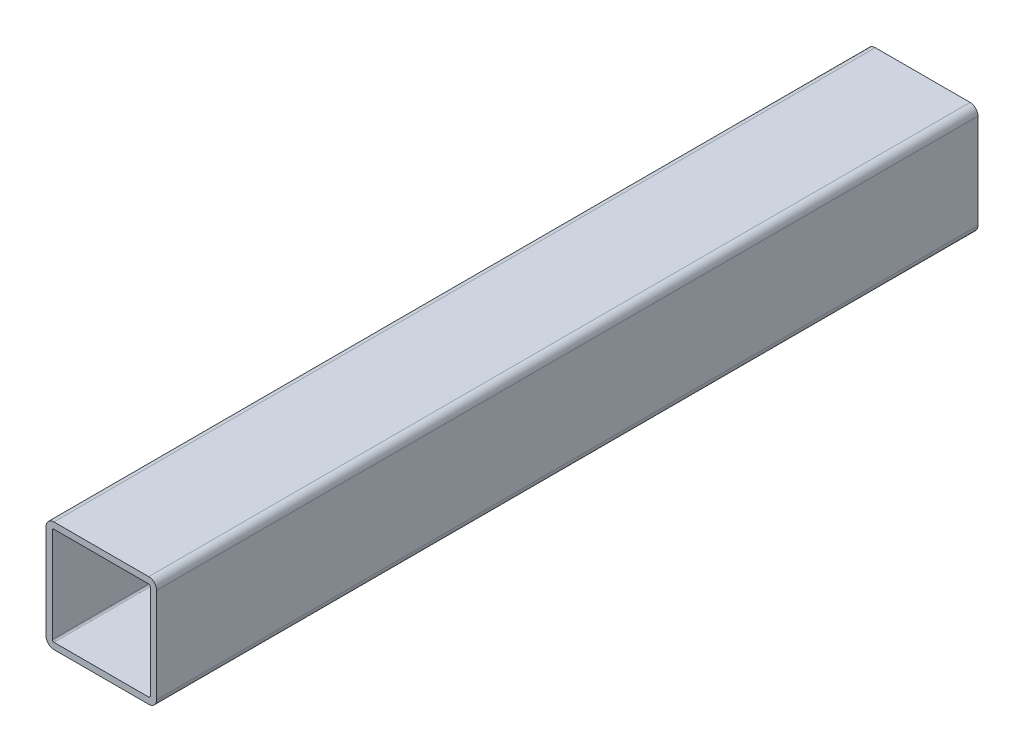
SolidWorks part; units mm, degrees
material "Plain Carbon Steel"
ref_plane "Front Plane" through (0, 0, 0) normal (0, 0, 1) x (1, 0, 0)
ref_plane "Top Plane" through (0, 0, 0) normal (0, 1, 0) x (1, 0, 0)
ref_plane "Right Plane" through (0, 0, 0) normal (1, 0, 0) x (0, 0, -1)
sketch "Sketch1" plane through (0, 0, 0) normal (0, 0, 1) x (1, 0, 0)
  line L0 (4, 5) -> (4, 65)
  line L1 (5, 0) -> (65, 0)
  line L2 (0, 5) -> (0, 65)
  line L3 (5, 70) -> (65, 70)
  line L4 (70, 5) -> (70, 65)
  line L5 (5, 66) -> (65, 66)
  line L6 (66, 5) -> (66, 65)
  line L7 (5, 4) -> (65, 4)
  arc A0 (5, 0) -> (0, 5) centre (5, 5) cw
  arc A1 (65, 0) -> (70, 5) centre (65, 5) ccw
  arc A2 (65, 70) -> (70, 65) centre (65, 65) cw
  arc A3 (0, 65) -> (5, 70) centre (5, 65) cw
  arc A4 (4, 65) -> (5, 66) centre (5, 65) cw
  arc A5 (65, 66) -> (66, 65) centre (65, 65) cw
  arc A6 (65, 4) -> (66, 5) centre (65, 5) ccw
  arc A7 (5, 4) -> (4, 5) centre (5, 5) cw
  point P7 (0, 0)
  point P12 (70, 70)
  point P15 (0, 70)
  dimension "D3" = 5
  dimension "D1" = 70
  dimension "D2" = 70
  dimension "D4" = 4
extrude "Boss-Extrude1" add sketch "Sketch1" along normal blind 520
sketch "Center_lines" plane through (0, 70, 0) normal (0, 1, 0) x (1, 0, 0)
  line L0 (35, 58.7626) -> (35, -578.7626) construction
  line L1 (0, -260) -> (70, -260) construction
  line L2 (65, 0) -> (5, 0) construction
  line L3 (65, -520) -> (65, 0) construction
  line L4 (0, -520) -> (0, 0) construction
  point P6 (35, 0)
  point P7 (35, -260)
  point P10 (65, -260)
  point P15 (35, -260)
sketch "Tube_end_reference" plane through (0, 0, 520) normal (0, 0, 1) x (1, 0, 0)
  line L0 (70, 5) -> (70, 65) construction
  line L1 (70, 70) -> (0, 70) construction
  line L2 (70, 70) -> (70, 0) construction
  line L3 (70, 0) -> (0, 0) construction
  line L4 (0, 70) -> (0, 0) construction
  line L5 (0, 65) -> (0, 5) construction
  line L6 (0, 70) -> (70, 70) construction
  line L7 (5, 0) -> (65, 0) construction
sketch "Tube_corners_R" plane through (70, 0, 0) normal (1, 0, 0) x (0, 0, -1)
  line L0 (-520, 0) -> (0, 0) construction
  line L1 (-520, 70) -> (0, 70) construction
sketch "Tube_corners_L" plane through (0, 0, 0) normal (-1, 0, 0) x (0, 0, 1)
  line L0 (520, 70) -> (0, 70) construction
  line L1 (520, 0) -> (0, 0) construction
